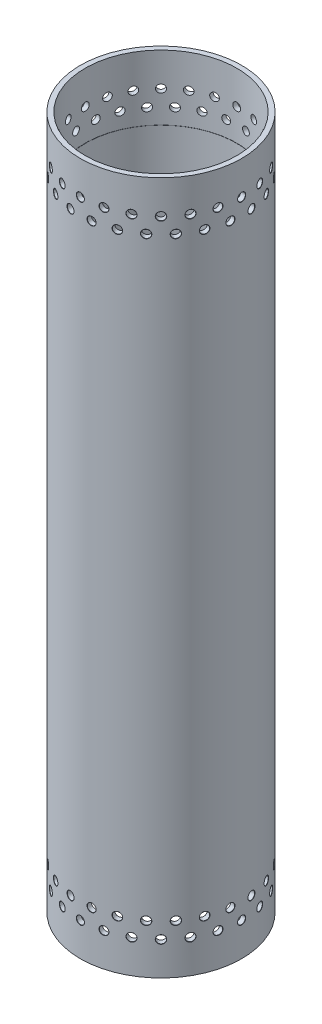
SolidWorks part; units mm, degrees
material "AW-6082-T6 (PA4)"
ref_plane "Płaszczyzna przednia" through (0, 0, 0) normal (0, 0, 1) x (1, 0, 0)
ref_plane "Płaszczyzna górna" through (0, 0, 0) normal (0, 1, 0) x (1, 0, 0)
ref_plane "Płaszczyzna prawa" through (0, 0, 0) normal (1, 0, 0) x (0, 0, -1)
sketch "Szkic1" plane through (0, 0, 0) normal (0, 1, 0) x (1, 0, 0)
  circle A0 centre (0, 0) radius 90
  circle A1 centre (0, 0) radius 81.5
  dimension "D1" = 8.5
  dimension "D2" = 180
  dimension "D3" = 163
extrude "Dodanie-wyciągnięcie1" add sketch "Szkic1" along normal blind 747
sketch "Szkic2" plane through (0, 747, 0) normal (0, 1, 0) x (1, 0, 0)
  circle A0 centre (0, 0) radius 87
  circle A1 centre (0, 0) radius 90 construction
  circle A2 centre (0, 0) radius 90
  dimension "D1" = 174
extrude "Wytnij-wyciągnięcie1" cut sketch "Szkic2" against normal through all
sketch "Szkic3" plane through (0, 747, 0) normal (0, 1, 0) x (1, 0, 0)
  circle A0 centre (0, 0) radius 81.7
  circle A1 centre (0, 0) radius 81.5 construction
  circle A2 centre (0, 0) radius 81.5
  dimension "D1" = 0.2
extrude "Wytnij-wyciągnięcie2" cut sketch "Szkic3" against normal blind 70
ref_plane "Płaszczyzna1" through (0, 0, 87) normal (0, 0, 1) x (1, 0, 0)
ref_plane "Płaszczyzna2" through (11.3558, 0, 86.2557) normal (0.1305, 0, 0.9914) x (0, 1, 0)
hole_wizard "Otwór Ø8.5 (8.5)1" positions "Szkic5" profile "Szkic6" hole size "Ø8.5" standard "DIN" end condition up to next
sketch "Szkic5" plane through (0, 0, 87) normal (0, 0, 1) x (1, 0, 0)
  line L0 (87, 747) -> (-87, 747) construction
  line L1 (87, 0) -> (87, 747) construction
  line L2 (-87, 747) -> (-87, 0) construction
  line L3 (87, 0) -> (87, 747)
  line L4 (-87, 747) -> (-87, 0)
  line L5 (0, 869.2816) -> (0, 760.9563) construction
  point P0 (0, 711)
  dimension "D1" = 36
sketch "Szkic6" plane through (0, 711, 87) normal (1, 0, 0) x (0, -1, 0)
  line L0 (0, 0) -> (0, 5.3)
  line L1 (0, 5.3) -> (4.25, 5.3)
  line L2 (4.25, 5.3) -> (4.25, 0.25)
  line L3 (4.25, 0.25) -> (4.5, 0)
  line L5 (4.5, 0) -> (0, 0)
  line L6 (-4.25, 0.25) -> (-4.5, 0) construction
  line L11 (0, -6.35) -> (0, 107.95) construction
  dimension "Średnica otworu na wylot" = 8.5
  dimension "Głębokość otworu na wylot" = 5.3
  dimension "Średnica zewnętrznego pogłębienia stożkowego" = 9
  dimension "Kąt zewnętrznego pogłębienia stożkowego" = 90
hole_wizard "Otwór Ø8.5 (8.5)2" positions "Szkic7" profile "Szkic8" hole size "Ø8.5" standard "BSI" end condition up to next
sketch "Szkic7" plane through (11.3558, 0, 86.2557) normal (0.1305, 0, 0.9914) x (0, 1, 0)
  line L0 (747, -87) -> (747, 87) construction
  line L1 (0, -87) -> (747, -87) construction
  line L2 (747, 87) -> (0, 87) construction
  line L3 (0, -87) -> (747, -87)
  line L4 (747, 87) -> (0, 87)
  line L5 (862.9512, 0) -> (744.0524, 0) construction
  ellipse E0 centre (711, 11.3231) end of major axis (715.25, 11.3231) minor radius 4.2136 construction
  point P0 (694, 0)
  dimension "D1" = 53
  dimension "D2" = 20.4258
sketch "Szkic8" plane through (11.3558, 694, 86.2557) normal (0, 1, 0) x (0.9914, 0, -0.1305)
  line L0 (0, 0) -> (0, 5.3)
  line L1 (0, 5.3) -> (4.25, 5.3)
  line L2 (4.25, 5.3) -> (4.25, 0.25)
  line L3 (4.25, 0.25) -> (4.5, 0)
  line L5 (4.5, 0) -> (0, 0)
  line L6 (-4.25, 0.25) -> (-4.5, 0) construction
  line L11 (0, -6.35) -> (0, 107.95) construction
  dimension "Średnica otworu na wylot" = 8.5
  dimension "Głębokość otworu na wylot" = 5.3
  dimension "Średnica zewnętrznego pogłębienia stożkowego" = 9
  dimension "Kąt zewnętrznego pogłębienia stożkowego" = 90
pattern_circular "Szyk kołowy1" count 24 over 360 about axis through (0, 0, 0) along (0, 1, 0) of "Otwór Ø8.5 (8.5)1", "Otwór Ø8.5 (8.5)2"
ref_plane "Płaszczyzna3" through (0, 373.5, 0) normal (0, 1, 0) x (1, 0, 0)
mirror "Lustro1" about plane through (0, 373.5, 0) normal (0, 1, 0) of "Otwór Ø8.5 (8.5)2", "Otwór Ø8.5 (8.5)1", "Szyk kołowy1", "Wytnij-wyciągnięcie2"
